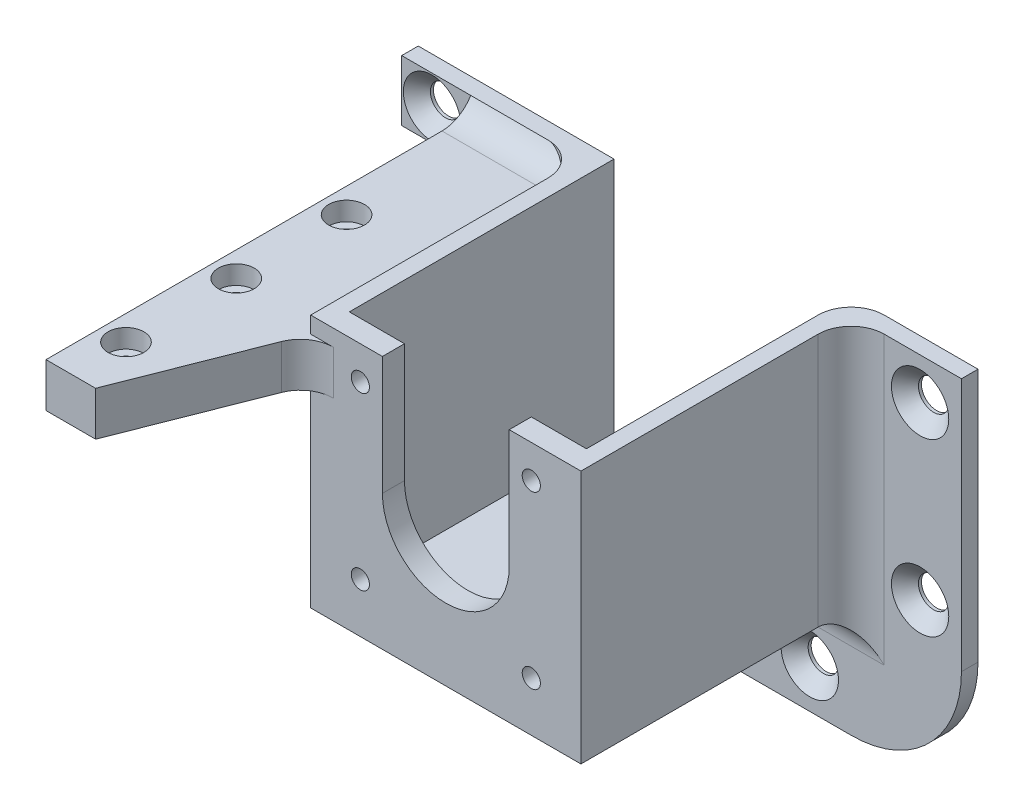
SolidWorks part; units mm, degrees
ref_plane "Plan de face" through (0, 0, 0) normal (0, 0, 1) x (1, 0, 0)
ref_plane "Plan de dessus" through (0, 0, 0) normal (0, 1, 0) x (1, 0, 0)
ref_plane "Plan de droite" through (0, 0, 0) normal (1, 0, 0) x (0, 0, -1)
sketch "Esquisse1" plane through (0, 0, 0) normal (0, 0, 1) x (1, 0, 0)
  line L0 (-11.5, 0) -> (-11.5, 21.5)
  line L1 (24.5, -24.5) -> (-24.5, -24.5)
  line L2 (24.5, -24.5) -> (24.5, 21.5)
  line L3 (24.5, 21.5) -> (11.5, 21.5)
  line L4 (-24.5, -24.5) -> (-24.5, 21.5)
  line L5 (11.5, 0) -> (11.5, 21.5)
  line L6 (-11.5, 21.5) -> (-24.5, 21.5)
  line L7 (15.5, -15.5) -> (-15.5, -15.5) construction
  line L8 (15.5, -15.5) -> (15.5, 15.5) construction
  line L9 (15.5, 15.5) -> (-15.5, 15.5) construction
  line L10 (-15.5, -15.5) -> (-15.5, 15.5) construction
  line L11 (15.5, -15.5) -> (-15.5, 15.5) construction
  line L12 (15.5, 15.5) -> (-15.5, -15.5) construction
  circle A0 centre (-15.5, 15.5) radius 1.65
  circle A1 centre (15.5, 15.5) radius 1.65
  circle A2 centre (15.5, -15.5) radius 1.65
  circle A3 centre (-15.5, -15.5) radius 1.65
  arc A4 (-11.5, 0) -> (11.5, 0) centre (0, 0) ccw
  point P0 (0, 0)
  point P5 (0, 0)
  point P18 (0, -24.5)
  dimension "D1" = 3.3
  dimension "D2" = 31
  dimension "D3" = 23
  dimension "D4" = 49
  dimension "D5" = 24.5
  dimension "D6" = 21.5
extrude "Boss.-Extru.1" add sketch "Esquisse1" along normal mid plane 4
sketch "Esquisse2" plane through (0, 0, -2) normal (0, 0, -1) x (-1, 0, 0)
  line L0 (-24.5, 21.5) -> (-21.5, 21.5)
  line L1 (-24.5, 21.5) -> (-11.5, 21.5) construction
  line L2 (-21.5, 21.5) -> (-21.5, -21.5)
  line L3 (-21.5, -21.5) -> (21.5, -21.5)
  line L4 (21.5, -21.5) -> (21.5, 21.5)
  line L5 (11.5, 21.5) -> (24.5, 21.5) construction
  line L6 (21.5, 21.5) -> (24.5, 21.5)
  line L7 (24.5, 21.5) -> (24.5, -24.5)
  line L8 (24.5, -24.5) -> (-24.5, -24.5)
  line L9 (24.5, -24.5) -> (-24.5, -24.5) construction
  line L10 (-24.5, -24.5) -> (-24.5, 21.5)
  line L11 (-21.5, -21.5) -> (-21.5, -24.5) construction
  dimension "D1" = 3
extrude "Boss.-Extru.2" add sketch "Esquisse2" along normal blind 48
sketch "Esquisse4" plane through (0, 0, -50) normal (0, 0, -1) x (-1, 0, 0)
  line L0 (-24.5, 21.5) -> (-44.5, 21.5)
  line L1 (-44.5, 21.5) -> (-44.5, -24.5)
  line L2 (-44.5, -24.5) -> (-24.5, -24.5) construction
  line L5 (-37, 14) -> (-37, 21.5) construction
  line L6 (-37, 14) -> (-44.5, 14) construction
  line L8 (-24.5, -24.5) -> (-24.5, 21.5)
  line L14 (-24.5, -24.5) -> (24.5, -24.5)
  line L15 (-24.5, -24.5) -> (-24.5, -44.5) construction
  line L16 (24.5, -24.5) -> (24.5, -44.5)
  line L17 (-24.5, -44.5) -> (24.5, -44.5)
  line L18 (-37, -17) -> (-44.5, -17) construction
  line L19 (-37, -17) -> (-37, -24.5) construction
  line L20 (-17, -37) -> (-24.5, -37) construction
  line L21 (-17, -37) -> (-17, -44.5) construction
  line L22 (17, -37) -> (24.5, -37) construction
  line L23 (17, -37) -> (17, -44.5) construction
  circle A0 centre (-37, 14) radius 5.6 construction
  circle A4 centre (-37, -17) radius 5.6 construction
  circle A5 centre (-17, -37) radius 5.6 construction
  circle A6 centre (17, -37) radius 5.6 construction
  arc A7 (-44.5, -24.5) -> (-24.5, -44.5) centre (-24.5, -24.5) ccw
  line M3 (-24.5, 21.5) -> (-24.5, -24.5)
  line M4 (-24.5, -24.5) -> (24.5, -24.5)
  dimension "D1" = 11.2
  dimension "D2" = 20
  dimension "D3" = 7.5
extrude "Boss.-Extru.3" add sketch "Esquisse4" against normal blind 3 contours L1 L2 L0 M3 | L15 L17 L16 M4 region at (25.4548, -1.5, -50)
fillet "Congé1" radius 6 4 edges at (21.5, 0, -50) (0, -21.5, -50) (24.5, -1.5, -47) (0, -24.5, -47)
sketch "Esquisse6" plane through (-24.5, 0, 0) normal (-1, 0, 0) x (0, 0, 1)
  line L0 (-50, 18.5) -> (2, 18.5)
  line L1 (-50, 18.5) -> (-50, 10.5)
  line L2 (2, 18.5) -> (2, 10.5)
  line L3 (-50, 10.5) -> (2, 10.5)
  line L4 (-50, -44.5) -> (-50, 21.5) construction
  line L5 (2, 21.5) -> (2, -24.5) construction
  line L6 (2, 21.5) -> (-50, 21.5) construction
  dimension "D1" = 8
  dimension "D2" = 11
extrude "Boss.-Extru.4" add sketch "Esquisse6" along normal blind 20
sketch "Esquisse7" plane through (0, 18.5, 0) normal (0, 1, 0) x (1, 0, 0)
  line L0 (-44.5, -2) -> (-44.5, -30)
  line L1 (-44.5, -30) -> (-35.5, -30)
  line L2 (-35.5, -30) -> (-24.5, -2)
  line L3 (-44.5, 50) -> (-24.5, 50) construction
  line L4 (-44.5, -2) -> (-24.5, -2)
  dimension "D1" = 80
  dimension "D2" = 9
extrude "Boss.-Extru.5" add sketch "Esquisse7" against normal up to surface (8 mm away) up to face at (-34.5, 10.5, -24)
sketch "Esquisse8" plane through (0, 0, -50) normal (0, 0, -1) x (-1, 0, 0)
  line L0 (44.5, 10.5) -> (24.5, 10.5) construction
  line L1 (24.5, 21.5) -> (57, 21.5)
  line L2 (24.5, 21.5) -> (24.5, 10.5)
  line L3 (24.5, 10.5) -> (57, 10.5)
  line L4 (57, 21.5) -> (57, 10.5)
  line L5 (51.5, 10.5) -> (51.5, 16) construction
  line L6 (51.5, 16) -> (57, 16) construction
  line L7 (21.5, 21.5) -> (21.5, -27.5) construction
  circle A0 centre (51.5, 16) radius 5.2 construction
  dimension "D1" = 10.4
  dimension "D2" = 30
extrude "Boss.-Extru.7" add sketch "Esquisse8" against normal up to surface (3 mm away) up to face at (18.5203, -19.3774, -47)
hole_wizard "Fraisage pour vis à tête fraisée M51" positions "Esquisse3D1" profile "Esquisse5" countersink size "M5" standard "ISO" end condition through all
sketch3d "Esquisse3D1"
  point P34 (-17, -37, -47)
  point P36 (37, -17, -47)
  point P38 (37, 14, -47)
  point P41 (17, -37, -47)
  point P52 (-51.5, 16, -47)
sketch "Esquisse5" plane through (-17, -37, -47) normal (1, 0, 0) x (0, -1, 0)
  line L0 (0, 0) -> (0, 3)
  line L1 (0, 3) -> (2.75, 3)
  line L2 (2.75, 3) -> (2.75, 2.45)
  line L3 (2.75, 2.45) -> (5.2, 0)
  line L5 (5.2, 0) -> (0, 0)
  line L6 (-2.75, 2.45) -> (-5.2, 0) construction
  line L11 (0, -6.35) -> (0, 107.95) construction
  dimension "Diamètre du perçage jusqu'au prochain" = 5.5
  dimension "Profondeur du perçage jusqu'au prochain" = 3
  dimension "Diamètre du fraisage entrant" = 10.4
  dimension "Angle du fraisage entrant" = 90
fillet "Congé3" radius 6 2 edges at (-34.5, 18.5, -47) (-24.5, 20, -47)
fillet "Congé4" radius 6 1 edges at (-24.5, 14.5, 2)
sketch "Esquisse9" plane through (0, 18.5, 0) normal (0, 1, 0) x (1, 0, 0)
  line L0 (-44.5, -30) -> (-44.5, 41.8038) construction
  line L1 (-24.5, 50) -> (-57, 50) construction
  circle A0 centre (-40, 40) radius 1.8 construction
  circle A1 centre (-40, 20) radius 1.8
  circle A2 centre (-40, 0) radius 1.8
  circle A3 centre (-40, -20) radius 1.8
  dimension "D1" = 3.6
  dimension "D5" = 20
  dimension "D2" = 4.5
  dimension "D3" = 10
  dimension "D4" = 20
  dimension "D6" = 20
hole_wizard "Chambrage pour vis à six pans creux M31" positions "Esquisse3D2" profile "Esquisse10" counterbore size "M3" standard "ISO" end condition through all
sketch3d "Esquisse3D2"
  point P0 (-40, 18.5, -20)
  point P3 (-40, 18.5, 0)
  point P6 (-40, 18.5, 20)
sketch "Esquisse10" plane through (-40, 18.5, -20) normal (1, 0, 0) x (0, 0, 1)
  line L0 (0, 0) -> (0, 63)
  line L1 (0, 63) -> (1.7, 63)
  line L3 (1.7, 63) -> (1.7, 3.4)
  line L4 (1.7, 3.4) -> (3.25, 3.4)
  line L5 (3.25, 3.4) -> (3.25, 0)
  line L7 (3.25, 0) -> (0, 0)
  line L11 (0, -6.35) -> (0, 107.95) construction
  dimension "Diamètre du perçage jusqu'au prochain" = 3.4
  dimension "Profondeur du perçage jusqu'au prochain" = 63
  dimension "Diamètre du chambrage" = 6.5
  dimension "Profondeur du chambrage" = 3.4
